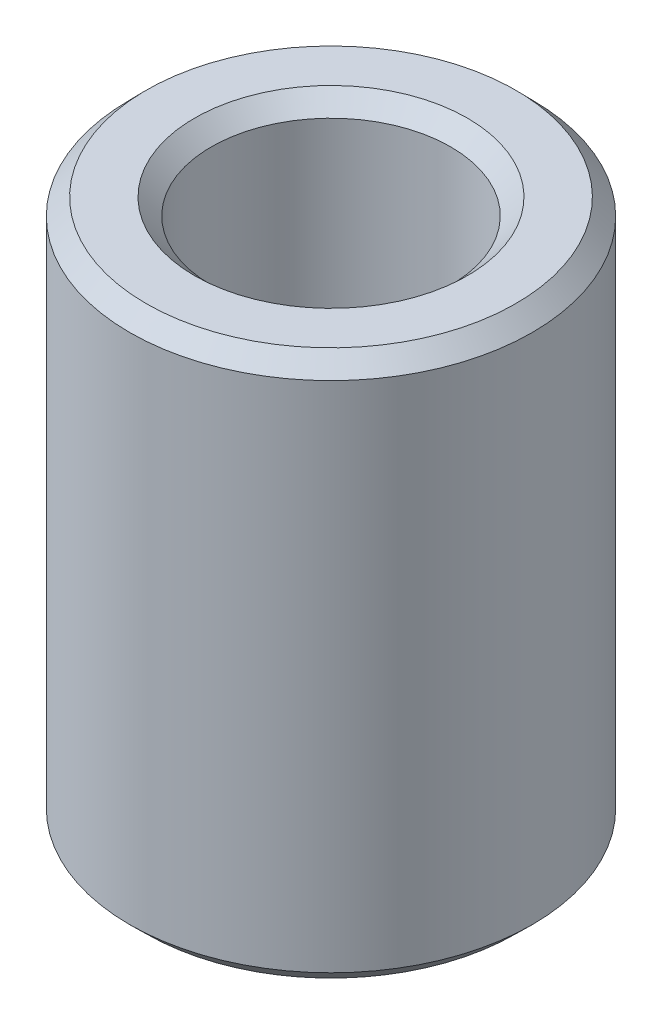
SolidWorks part; units mm, degrees
ref_plane "Front Plane" through (0, 0, 0) normal (0, 0, 1) x (1, 0, 0)
ref_plane "Top Plane" through (0, 0, 0) normal (0, 1, 0) x (1, 0, 0)
ref_plane "Right Plane" through (0, 0, 0) normal (1, 0, 0) x (0, 0, -1)
sketch "Sketch1" plane through (0, 0, 0) normal (0, 1, 0) x (1, 0, 0)
  circle A0 centre (0, 0) radius 12.5
  dimension "SLEEVE_OD" = 25
extrude "Boss-Extrude1" add sketch "Sketch1" along normal blind 33.9073
sketch "Sketch2" plane through (0, 0, 0) normal (0, 1, 0) x (1, 0, 0)
  circle A0 centre (0, 0) radius 7.4336
  dimension "BORE_D" = 14.8672
extrude "Cut-Extrude1" cut sketch "Sketch2" along normal through all
chamfer "Chamfer1" distance 1.0413 angle 44.482 4 edges at (0, 33.9073, 7.4336) (0, 0, 7.4336) (0, 0, 12.5) (0, 33.9073, 12.5) first distance on face at (0, 33.9073, 7.4336) first distance on face at (0, 0, 7.4336) first distance on face at (0, 33.9073, 12.5)
